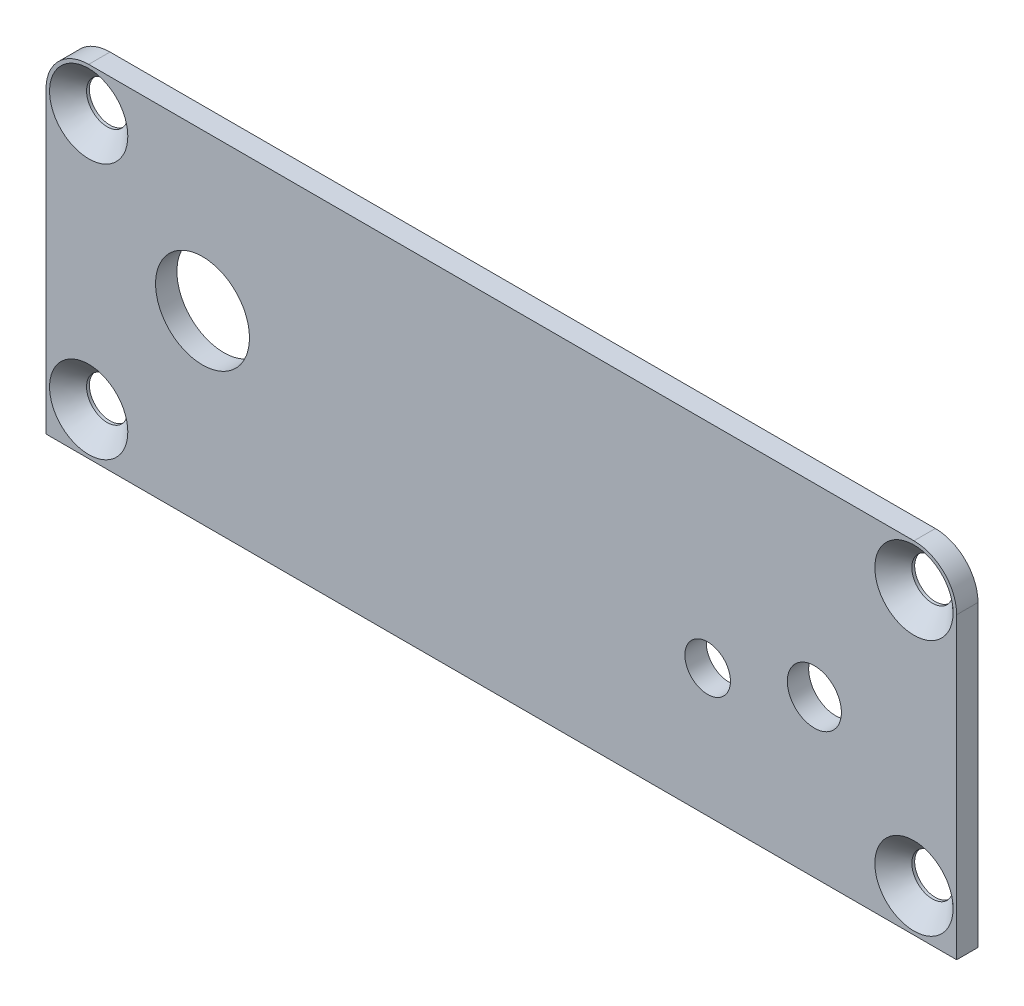
SolidWorks part; units mm, degrees
ref_plane "Front Plane" through (0, 0, 0) normal (0, 0, 1) x (1, 0, 0)
ref_plane "Top Plane" through (0, 0, 0) normal (0, 1, 0) x (1, 0, 0)
ref_plane "Right Plane" through (0, 0, 0) normal (1, 0, 0) x (0, 0, -1)
sketch "Sketch1" plane through (0, 0, 0) normal (0, 0, 1) x (1, 0, 0)
  line L1 (-32, 12) -> (32, 12)
  line L2 (-32, 12) -> (-32, -12)
  line L3 (-32, -12) -> (32, -12)
  line L4 (32, 12) -> (32, -12)
  line L5 (-32, 12) -> (32, -12) construction
  line L6 (-32, -12) -> (32, 12) construction
  point P0 (0, 0)
  dimension "D1" = 64
  dimension "D2" = 24
extrude "Boss-Extrude1" add sketch "Sketch1" against normal blind 1.5
hole_wizard "CSK for M2.5 Flat Head Machine Screw1" positions "Sketch3" profile "Sketch2" countersink size "M2.5" standard "ANSI Metric" end condition through all
sketch "Sketch3" plane through (0, 0, 0) normal (0, 0, 1) x (1, 0, 0)
  line L0 (32, 12) -> (-32, 12) construction
  line L1 (-32, 12) -> (-32, -12) construction
  line L2 (32, -12) -> (32, 12) construction
  line L3 (-32, -12) -> (32, -12) construction
  point P0 (-29, 9)
  point P7 (29, 9)
  point P11 (-29, -9)
  point P15 (29, -9)
  dimension "D1" = 3
  dimension "D2" = 3
  dimension "D3" = 3
  dimension "D4" = 3
sketch "Sketch2" plane through (-29, 9, 0) normal (1, 0, 0) x (0, -1, 0)
  line L0 (0, 0) -> (0, 1.5)
  line L1 (0, 1.5) -> (1.45, 1.5)
  line L2 (1.45, 1.5) -> (1.45, 1.3)
  line L3 (1.45, 1.3) -> (2.75, 0)
  line L5 (2.75, 0) -> (0, 0)
  line L6 (-1.45, 1.3) -> (-2.75, 0) construction
  line L11 (0, -6.35) -> (0, 107.95) construction
  dimension "Thru Hole Dia." = 2.9
  dimension "Thru Hole Depth" = 1.5
  dimension "Near C'Sink Dia." = 5.5
  dimension "Near C'Sink Angle" = 90
fillet "Fillet1" radius 3 2 edges at (-32, 12, -0.75) (32, 12, -0.75)
sketch "Sketch4" plane through (0, 0, 0) normal (0, 0, 1) x (1, 0, 0)
  circle A0 centre (-21, 1) radius 3.3
  dimension "D1" = 1
  dimension "D3" = 6.6
  dimension "D2" = 21
extrude "Cut-Extrude1" cut sketch "Sketch4" against normal through all
sketch "Sketch5" plane through (0, 0, 0) normal (0, 0, 1) x (1, 0, 0)
  circle A0 centre (14.5, -3) radius 1.6
  dimension "D1" = 3
  dimension "D3" = 3.2
  dimension "D2" = 14.5
extrude "Cut-Extrude2" cut sketch "Sketch5" against normal through all
sketch "Sketch6" plane through (0, 0, 0) normal (0, 0, 1) x (1, 0, 0)
  circle A0 centre (22, -1) radius 1.9
  dimension "D1" = 1
  dimension "D3" = 3.8
  dimension "D2" = 22
extrude "Cut-Extrude3" cut sketch "Sketch6" against normal through all
